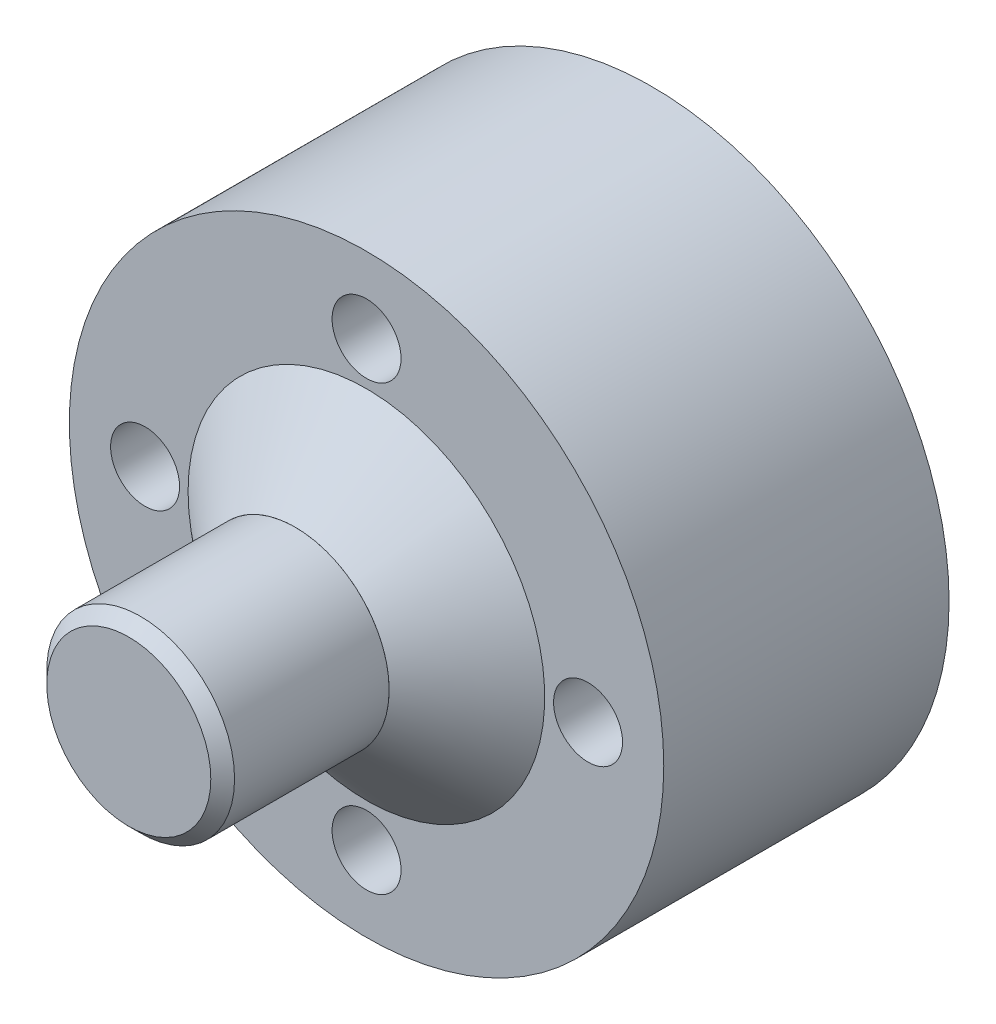
SolidWorks part; units mm, degrees
ref_plane "Front Plane" through (0, 0, 0) normal (0, 0, 1) x (1, 0, 0)
ref_plane "Top Plane" through (0, 0, 0) normal (0, 1, 0) x (1, 0, 0)
ref_plane "Right Plane" through (0, 0, 0) normal (1, 0, 0) x (0, 0, -1)
sketch "Sketch1" plane through (0, 0, 0) normal (0, 0, 1) x (1, 0, 0)
  circle A0 centre (0, 0) radius 12.5
  dimension "D2" = 25
extrude "Boss-Extrude1" add sketch "Sketch1" along normal mid plane 7
sketch "Sketch10" plane through (0, 0, 3.5) normal (0, 0, 1) x (1, 0, 0)
  circle A0 centre (0, 0) radius 12.5
  dimension "D1" = 25
sketch "Sketch8" plane through (0, 0, 3.5) normal (0, 0, 1) x (1, 0, 0)
  line L2 (-6.125, 6.125) -> (6.125, 6.125)
  line L3 (-6.125, 6.125) -> (-6.125, -6.125)
  line L4 (-6.125, -6.125) -> (6.125, -6.125)
  line L5 (6.125, 6.125) -> (6.125, -6.125)
  line L6 (-6.125, 6.125) -> (6.125, -6.125) construction
  line L7 (-6.125, -6.125) -> (6.125, 6.125) construction
  point P5 (0, 0)
  point P14 (0, 0)
  dimension "D1" = 12.25
extrude "Cut-Extrude1" cut sketch "Sketch8" against normal up to next
sketch "Sketch11" plane through (0, 0, 3.5) normal (0, 0, 1) x (1, 0, 0)
  line L0 (6.125, -6.125) -> (6.125, 6.125) construction
  circle A0 centre (9.315, 0) radius 1.45
  circle A1 centre (0, -9.315) radius 1.45
  circle A2 centre (-9.315, 0) radius 1.45
  circle A3 centre (0, 9.315) radius 1.45
  point P13 (0, 0)
  dimension "D1" = 2.9
  dimension "D2" = 3.19
  dimension "D3" = 4
extrude "Cut-Extrude4" cut sketch "Sketch11" against normal through all
sketch "Sketch14" plane through (0, 0, 3.5) normal (0, 0, 1) x (1, 0, 0)
  circle A0 centre (0, 0) radius 12.5
  circle A1 centre (0, 0) radius 12.5 construction
extrude "Boss-Extrude2" add sketch "Sketch14" along normal blind 5
sketch "Sketch13" plane through (0, 0, 0) normal (0, 1, 0) x (1, 0, 0)
  line L0 (0, -11.9651) -> (0, -27.8724) construction
  line L1 (0, -11.5) -> (3.95, -11.5)
  line L2 (-12.5, -8.5) -> (12.5, -8.5) construction
  line L3 (3.95, -11.5) -> (7.5, -8.5067)
  line L4 (7.5, -8.5067) -> (0, -8.5067)
  line L5 (0, -8.5067) -> (0, -11.5)
  point P10 (7.6127, -8.5067)
  point P14 (0, 0)
  dimension "D1" = 3.95
  dimension "D2" = 3
  dimension "D3" = 7.5
revolve "Revolve1" add sketch "Sketch13" angle 360 about L0
sketch "Sketch15" plane through (0, 0, 11.5) normal (0, 0, 1) x (1, 0, 0)
  circle A0 centre (0, 0) radius 3.95
extrude "Boss-Extrude3" add sketch "Sketch15" along normal blind 7
chamfer "Chamfer1" distance 0.5 angle 45 1 edges at (3.95, 0, 18.5)
sketch "Sketch18" plane through (0, 0, 8.5) normal (0, 0, 1) x (1, 0, 0)
  circle A0 centre (-9.315, 0) radius 1.45
  circle A1 centre (0, -9.315) radius 1.45
  circle A2 centre (9.315, 0) radius 1.45
  circle A3 centre (0, 9.315) radius 1.45
extrude "Cut-Extrude6" cut sketch "Sketch18" against normal blind 30
equation "\"drumDiameter\"= 25"
equation "\"D2@Sketch1\"= \"drumDiameter\""
equation "\"drumLength\"=7"
equation "\"foamThickness\"= 5"
equation "\"drumAbove\"= 0.6"
equation "\"holderThicc\"= 2"
equation "\"D1@Boss-Extrude1\"=\"drumLength\""
equation "\"squareBarLength\"= 12.25"
equation "\"D1@Sketch8\"=\"squareBarLength\""
equation "\"D1@Sketch10\"=\"drumDiameter\""
equation "\"toothlen\"= 2.5"
